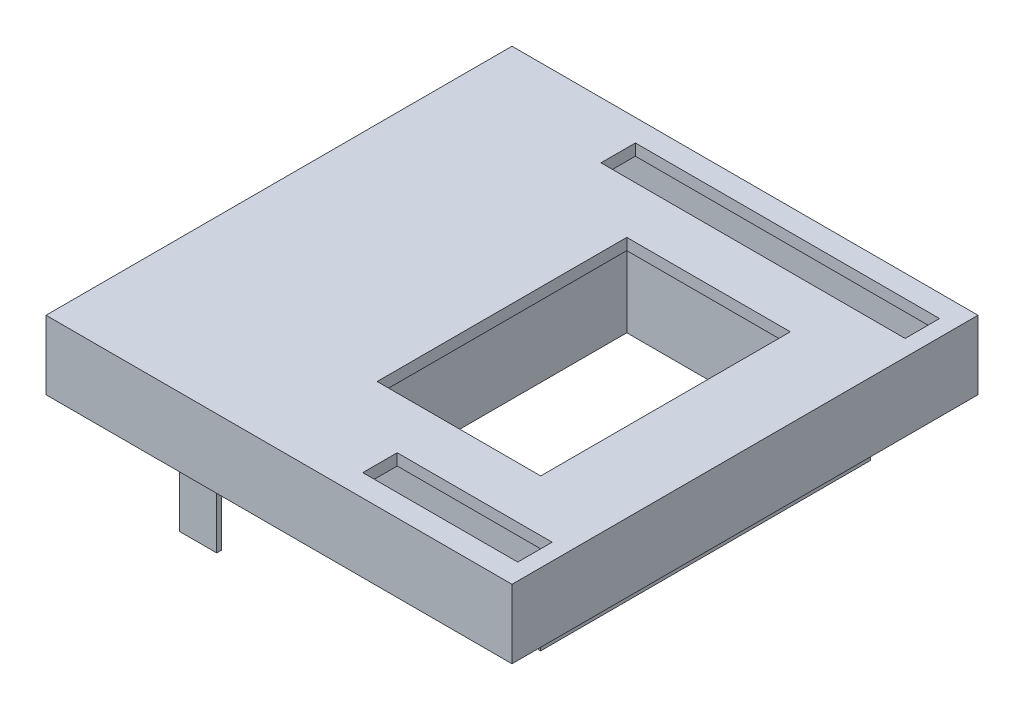
SolidWorks part; units mm, degrees
ref_plane "Front Plane" through (0, 0, 0) normal (0, 0, 1) x (1, 0, 0)
ref_plane "Top Plane" through (0, 0, 0) normal (0, 1, 0) x (1, 0, 0)
ref_plane "Right Plane" through (0, 0, 0) normal (1, 0, 0) x (0, 0, -1)
sketch "Sketch1" plane through (0, 0, 0) normal (0, 1, 0) x (1, 0, 0)
  line L0 (0.85, 0.85) -> (78.35, 0.85) construction
  line L1 (0, 0) -> (79.2, 0) construction
  line L2 (0, 0) -> (0, 79.2) construction
  line L3 (0, 79.2) -> (79.2, 79.2) construction
  line L4 (79.2, 0) -> (79.2, 79.2) construction
  line L5 (78.35, 0.85) -> (78.35, 78.35) construction
  line L6 (0.85, 78.35) -> (78.35, 78.35) construction
  line L7 (0.85, 0.85) -> (0.85, 78.35) construction
  dimension "D1" = 79.2
  dimension "D2" = 0.85
sketch "Sketch5" plane through (0, 0, 0) normal (0, 1, 0) x (1, 0, 0)
  line L0 (0, 0) -> (79.2, 0) construction
  line L1 (-1, -1) -> (80.2, -1)
  line L2 (-1, -1) -> (-1, 80.2)
  line L3 (-1, 80.2) -> (80.2, 80.2)
  line L4 (80.2, -1) -> (80.2, 80.2)
  line L5 (0, 0) -> (0, 79.2) construction
  line L6 (0, 79.2) -> (79.2, 79.2) construction
  dimension "D1" = 1
  dimension "D2" = 1
  dimension "D3" = 1
extrude "Boss-Extrude3" add sketch "Sketch5" along normal blind 2
sketch "Sketch9" plane through (0, 0, 0) normal (0, -1, 0) x (1, 0, 0)
  line L0 (0.85, -0.85) -> (78.35, -0.85) construction
  line L1 (1.85, -1.85) -> (77.35, -1.85)
  line L2 (1.85, -1.85) -> (1.85, -77.35)
  line L3 (1.85, -77.35) -> (77.35, -77.35)
  line L4 (77.35, -1.85) -> (77.35, -77.35)
  line L5 (0.85, -0.85) -> (0.85, -78.35) construction
  line L7 (0.85, -78.35) -> (78.35, -78.35) construction
  line L9 (78.35, -0.85) -> (78.35, -78.35) construction
  line L11 (80.2, 1) -> (-1, 1)
  line L12 (80.2, 1) -> (80.2, -80.2)
  line L13 (80.2, -80.2) -> (-1, -80.2)
  line L14 (-1, 1) -> (-1, -80.2)
  dimension "D1" = 1
  dimension "D2" = 1
  dimension "D3" = 1
  dimension "D4" = 1
extrude "Boss-Extrude5" add sketch "Sketch9" along normal blind 5
sketch "Sketch6" plane through (0, 0, 0) normal (0, -1, 0) x (1, 0, 0)
  line L0 (0.85, -0.85) -> (78.35, -0.85) construction
  line L1 (30.85, -10.85) -> (73.35, -10.85)
  line L2 (30.85, -10.85) -> (30.85, -68.35)
  line L3 (30.85, -68.35) -> (73.35, -68.35)
  line L4 (73.35, -10.85) -> (73.35, -68.35)
  line L5 (0.85, -78.35) -> (78.35, -78.35) construction
  line L6 (78.35, -0.85) -> (78.35, -78.35) construction
  line L7 (0.85, -0.85) -> (0.85, -78.35) construction
  line L8 (32.85, -12.85) -> (71.35, -12.85)
  line L9 (71.35, -12.85) -> (71.35, -66.35)
  line L10 (32.85, -66.35) -> (71.35, -66.35)
  line L11 (32.85, -12.85) -> (32.85, -66.35)
  dimension "D1" = 10
  dimension "D2" = 10
  dimension "D3" = 5
  dimension "D4" = 30
  dimension "D5" = 2
extrude "Boss-Extrude4" add sketch "Sketch6" along normal offset from surface (17.4 mm away) 12.4 up to face at (39.6, -5, -39.6) offset beyond the face yes
sketch "Sketch7" plane through (0, 0, 0) normal (0, -1, 0) x (1, 0, 0)
  line L0 (71.35, -12.85) -> (32.85, -12.85) construction
  line L1 (37.85, -17.85) -> (66.35, -17.85)
  line L2 (37.85, -17.85) -> (37.85, -61.35)
  line L3 (37.85, -61.35) -> (66.35, -61.35)
  line L4 (66.35, -17.85) -> (66.35, -61.35)
  line L5 (32.85, -12.85) -> (32.85, -66.35) construction
  line L6 (32.85, -66.35) -> (71.35, -66.35) construction
  line L7 (71.35, -66.35) -> (71.35, -12.85) construction
  line L8 (78.35, -0.85) -> (78.35, -78.35) construction
  line L9 (77.35, -2.85) -> (50.35, -2.85)
  line L10 (77.35, -2.85) -> (77.35, -8.85)
  line L11 (77.35, -8.85) -> (50.35, -8.85)
  line L12 (50.35, -2.85) -> (50.35, -8.85)
  line L13 (24.35, -76.35) -> (77.35, -76.35)
  line L14 (24.35, -76.35) -> (24.35, -70.35)
  line L15 (24.35, -70.35) -> (77.35, -70.35)
  line L16 (77.35, -76.35) -> (77.35, -70.35)
  line L17 (0.85, -78.35) -> (78.35, -78.35) construction
  line L18 (0.85, -0.85) -> (78.35, -0.85) construction
  dimension "D1" = 5
  dimension "D2" = 5
  dimension "D3" = 5
  dimension "D4" = 5
  dimension "D5" = 1
  dimension "D6" = 2
  dimension "D7" = 8
  dimension "D8" = 1
  dimension "D9" = 2
  dimension "D10" = 8
  dimension "D11" = 28
  dimension "D12" = 54
extrude "Cut-Extrude1" cut sketch "Sketch7" against normal up to surface (2 mm away) up to face at (39.6, 2, -39.6)
sketch "Sketch10" plane through (0, -5, 0) normal (0, -1, 0) x (1, 0, 0)
  line L1 (21.25, 0) -> (27.75, 0)
  line L2 (21.25, 0) -> (21.25, -0.85)
  line L3 (21.25, -0.85) -> (27.75, -0.85)
  line L4 (27.75, 0) -> (27.75, -0.85)
  line L6 (0.85, -0.85) -> (0.85, -78.35) construction
  line L7 (0, 0) -> (79.2, 0) construction
  line L8 (0.85, -0.85) -> (78.35, -0.85) construction
  point P4 (0, 0)
  point P10 (0, 0)
  dimension "D1" = 20.4
  dimension "D2" = 6.5
extrude "Boss-Extrude6" add sketch "Sketch10" along normal blind 15
sketch "Sketch11" plane through (0, -5, 0) normal (0, -1, 0) x (-1, 0, 0)
  line L0 (1, -1) -> (1, 80.2) construction
  line L1 (-1.85, 77.35) -> (-77.35, 77.35)
  line L2 (-1.85, 77.35) -> (-1.85, 1.85)
  line L3 (-1.85, 1.85) -> (-77.35, 1.85)
  line L4 (-77.35, 77.35) -> (-77.35, 1.85)
  line L5 (-78.35, 0.85) -> (-0.85, 0.85)
  line L6 (-78.35, 0.85) -> (-78.35, 78.35)
  line L7 (-78.35, 78.35) -> (-0.85, 78.35)
  line L8 (-0.85, 0.85) -> (-0.85, 78.35)
  line L9 (0, 79.2) -> (-79.2, 79.2)
  line L10 (0, 79.2) -> (0, 0)
  line L11 (0, 0) -> (-79.2, 0)
  line L12 (-79.2, 79.2) -> (-79.2, 0)
  line L13 (-80.2, -1) -> (1, -1)
  line L14 (-80.2, -1) -> (-80.2, 81.0483)
  line L15 (-80.2, 81.0483) -> (1, 81.0483)
  line L16 (1, -1) -> (1, 81.0483)
  line M13 (-1.85, 77.35) -> (-1.85, 1.85)
  line M14 (-1.85, 1.85) -> (-77.35, 1.85)
  line M15 (-77.35, 1.85) -> (-77.35, 77.35)
  line M16 (-77.35, 77.35) -> (-1.85, 77.35)
  line M17 (-80.2, 80.2) -> (-80.2, -1)
  line M18 (-80.2, -1) -> (1, -1)
  line M19 (1, -1) -> (1, 80.2)
  line M20 (1, 80.2) -> (-80.2, 80.2)
  line M22 (-21.25, 0) -> (-27.75, 0)
  line M24 (-27.75, 0.85) -> (-21.25, 0.85)
extrude "Boss-Extrude7" add sketch "Sketch11" along normal blind 5 contours L12 L9 L10 L11 M20 M17 M18 M19 M24 | L5 L8 L7 L6 M22 M16 M13 M14 M15 region at (78.2404, -5, -39.6) region at (80.0852, -5, -39.6)
